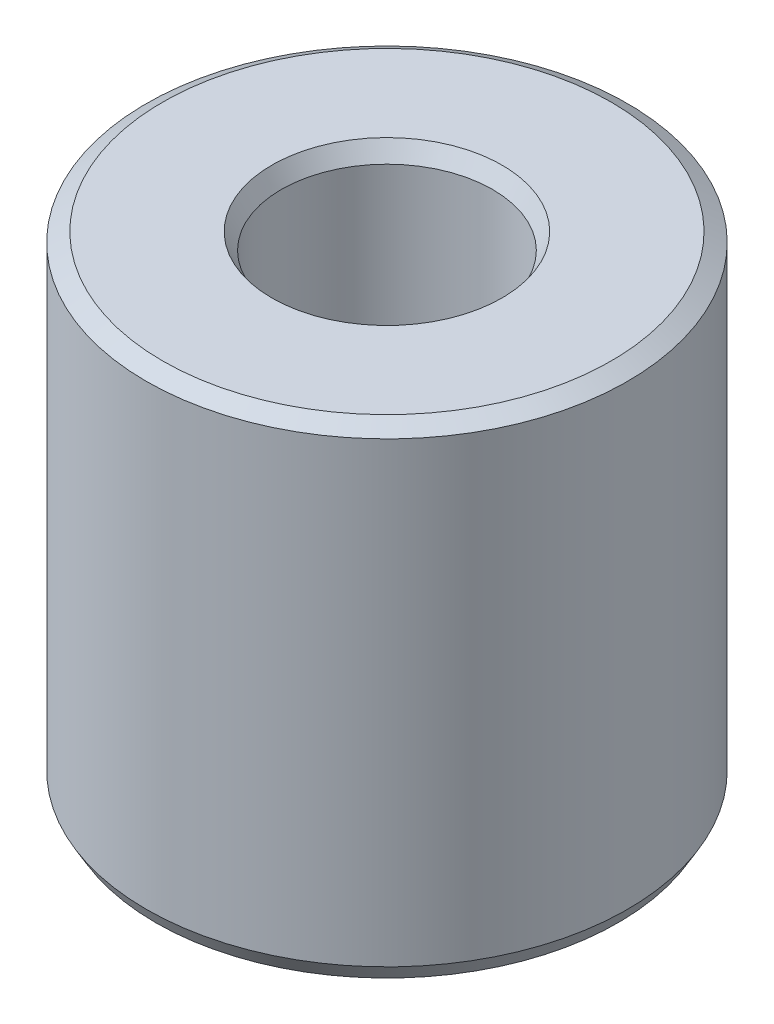
SolidWorks part; units mm, degrees
ref_plane "Front Plane" through (0, 0, 0) normal (0, 0, 1) x (1, 0, 0)
ref_plane "Top Plane" through (0, 0, 0) normal (0, 1, 0) x (1, 0, 0)
ref_plane "Right Plane" through (0, 0, 0) normal (1, 0, 0) x (0, 0, -1)
sketch "Sketch1" plane through (0, 0, 0) normal (0, 1, 0) x (1, 0, 0)
  circle A0 centre (0, 0) radius 7.5
  dimension "SLEEVE_OD" = 15
extrude "Boss-Extrude1" add sketch "Sketch1" along normal blind 15.0571
sketch "Sketch2" plane through (0, 0, 0) normal (0, 1, 0) x (1, 0, 0)
  circle A0 centre (0, 0) radius 3.2936
  dimension "BORE_D" = 6.5873
extrude "Cut-Extrude1" cut sketch "Sketch2" along normal through all
chamfer "Chamfer1" distance 0.2945 angle 60 4 edges at (0, 15.0571, 3.2936) (0, 0, 3.2936) (0, 0, 7.5) (0, 15.0571, 7.5) first distance on face at (0, 15.0571, 3.2936) first distance on face at (0, 0, 3.2936) first distance on face at (0, 15.0571, 7.5)
